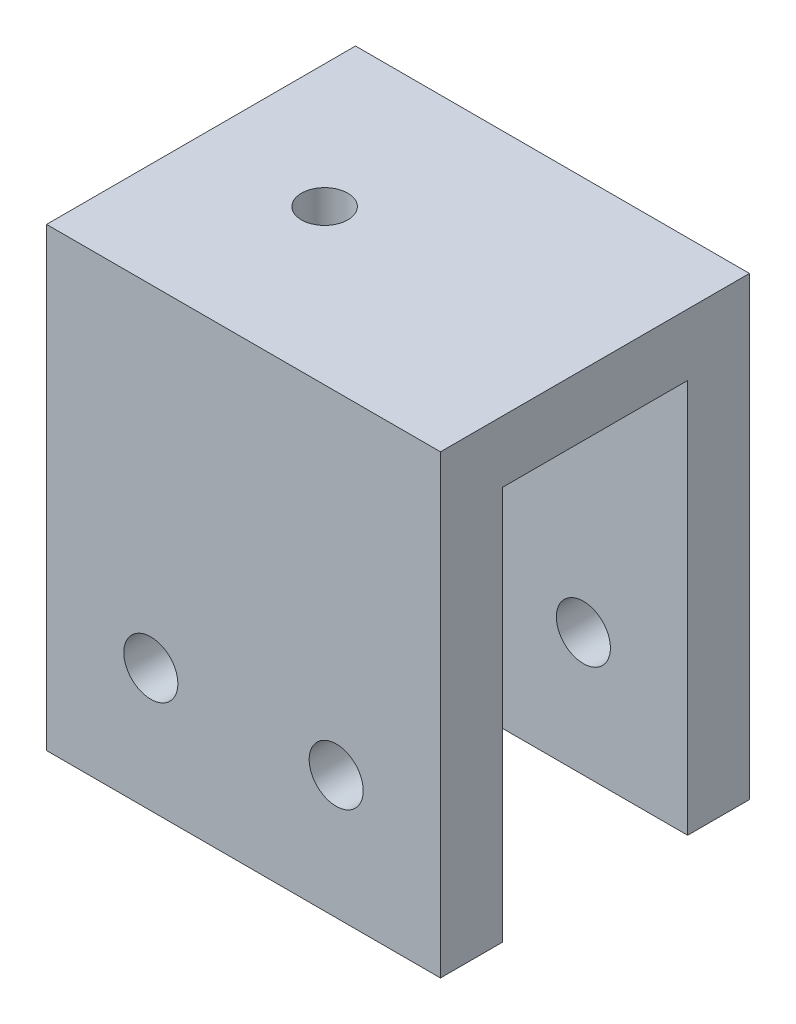
SolidWorks part; units mm, degrees
ref_plane "Płaszczyzna przednia" through (0, 0, 0) normal (0, 0, 1) x (1, 0, 0)
ref_plane "Płaszczyzna górna" through (0, 0, 0) normal (0, 1, 0) x (1, 0, 0)
ref_plane "Płaszczyzna prawa" through (0, 0, 0) normal (1, 0, 0) x (0, 0, -1)
sketch "Sketch1" plane through (0, 0, 0) normal (0, 0, 1) x (1, 0, 0)
  line L1 (0, 0) -> (-12.75, 0)
  line L2 (0, 0) -> (0, 12.75)
  line L3 (0, 12.75) -> (-12.75, 12.75)
  line L4 (-12.75, 0) -> (-12.75, 12.75)
  line L5 (0, 0) -> (-12.75, 12.75) construction
  line L6 (0, 12.75) -> (-12.75, 0) construction
  point P4 (-6.375, 6.375)
  dimension "D1" = 12.75
  dimension "D2" = 12.75
extrude "Boss-Extrude1" add sketch "Sketch1" along normal blind 2 contours L2 L1 L4 L3
ref_plane "Plane1" through (0, 0, -6) normal (0, 0, -1) x (-1, 0, 0)
sketch "Sketch2" plane through (0, 0, -6) normal (0, 0, -1) x (-1, 0, 0)
  line L4 (12.75, 12.75) -> (0, 12.75)
  line L5 (0, 12.75) -> (0, 0)
  line L6 (0, 0) -> (12.75, 0)
  line L7 (12.75, 0) -> (12.75, 12.75)
  line L8 (12.75, 12.75) -> (0, 12.75)
  line L9 (0, 12.75) -> (0, 0)
  line L10 (0, 0) -> (12.75, 0)
  line L11 (12.75, 0) -> (12.75, 12.75)
  dimension "D1" = 0
extrude "Boss-Extrude2" add sketch "Sketch2" along normal blind 2 separate body
sketch "Sketch3" plane through (0, 12.75, 0) normal (0, 1, 0) x (1, 0, 0)
  line L1 (0, -2) -> (-12.75, -2)
  line L2 (0, -2) -> (0, 8)
  line L3 (0, 8) -> (-12.75, 8)
  line L4 (-12.75, -2) -> (-12.75, 8)
  line L5 (0, -2) -> (-12.75, 8) construction
  line L6 (0, 8) -> (-12.75, -2) construction
  point P4 (-6.375, 3)
extrude "Boss-Extrude3" add sketch "Sketch3" along normal blind 2
hole_wizard "Ø1.0mm Dowel Hole1" positions "Sketch4" profile "Sketch5" hole size "Ø1.0" standard "ANSI Metric" end condition through all
sketch "Sketch4" plane through (0, 0, 2) normal (0, 0, 1) x (1, 0, 0)
  line L0 (-12.75, 0) -> (-12.75, 14.75) construction
  line L1 (0, 0) -> (-12.75, 0) construction
  point P0 (-9.375, 4)
  point P2 (-3.375, 4)
  dimension "D1" = 6
  dimension "D2" = 3.375
  dimension "D3" = 4
sketch "Sketch5" plane through (-9.375, 4, 2) normal (1, 0, 0) x (0, -1, 0)
  line L0 (0, 0) -> (0, 10)
  line L1 (0, 10) -> (0.875, 10)
  line L2 (0.875, 10) -> (0.875, 0)
  line L5 (0.875, 0) -> (0, 0)
  line L11 (0, -6.35) -> (0, 107.95) construction
  dimension "Thru Hole Dia." = 1.75
  dimension "Thru Hole Depth" = 10
hole_wizard "Ø1.0mm Dowel Hole2" positions "Sketch6" profile "Sketch7" hole size "Ø1.0" standard "ANSI Metric" end condition through all
sketch "Sketch6" plane through (0, 14.75, 0) normal (0, 1, 0) x (1, 0, 0)
  line L0 (-12.75, 8) -> (-12.75, -2) construction
  line L4 (0, 8) -> (-12.75, 8) construction
  point P0 (-8.75, 3)
  dimension "D1" = 4
  dimension "D2" = 5
sketch "Sketch7" plane through (-8.75, 14.75, -3) normal (1, 0, 0) x (0, 0, 1)
  line L0 (0, 0) -> (0, 14.75)
  line L1 (0, 14.75) -> (0.75, 14.75)
  line L2 (0.75, 14.75) -> (0.75, 0)
  line L5 (0.75, 0) -> (0, 0)
  line L11 (0, -6.35) -> (0, 107.95) construction
  dimension "Thru Hole Dia." = 1.5
  dimension "Thru Hole Depth" = 14.75
